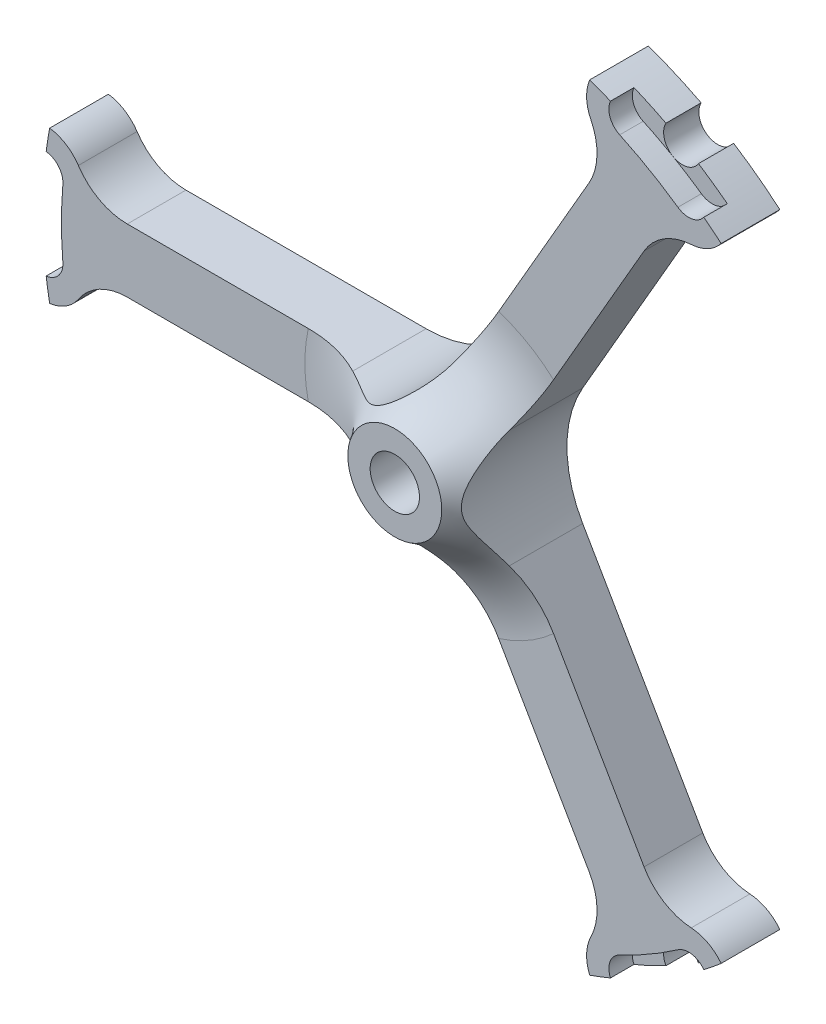
SolidWorks part; units mm, degrees
ref_plane "Plan de face" through (0, 0, 0) normal (0, 0, 1) x (1, 0, 0)
ref_plane "Plan de dessus" through (0, 0, 0) normal (0, 1, 0) x (1, 0, 0)
ref_plane "Plan de droite" through (0, 0, 0) normal (1, 0, 0) x (0, 0, -1)
sketch "Esquisse1" plane through (0, 0, 0) normal (0, 0, 1) x (1, 0, 0)
  line L19 (-1000, 0) -> (49000, 0) construction
  line L21 (-27.7888, 2.7) -> (-7.3323, 2.7)
  line L23 (-27.7888, -2.7) -> (-7.3323, -2.7)
  line L33 (16.2327, 22.7158) -> (6.0044, 5)
  line L34 (11.5561, 25.4158) -> (1.3279, 7.7)
  line L35 (11.5561, -25.4158) -> (1.3279, -7.7)
  line L36 (16.2327, -22.7158) -> (6.0044, -5)
  arc A0 (-34.3972, 6.4678) -> (-34.6976, 4.5906) centre (0, 0) ccw
  arc A7 (-33.2771, 2.8629) -> (-34.6976, 4.5906) centre (-34.8712, 3) ccw
  arc A8 (-33.2771, -2.8629) -> (-34.6976, -4.5906) centre (-34.8712, -3) cw
  arc A12 (-33.2771, 2.8629) -> (-33.2771, -2.8629) centre (0, 0) ccw
  arc A13 (-31.9549, 4.9353) -> (-34.3972, 6.4678) centre (-34.8712, 3) ccw
  arc A14 (-31.9549, -4.9353) -> (-34.3972, -6.4678) centre (-34.8712, -3) cw
  arc A15 (-34.6976, -4.5906) -> (-34.3972, -6.4678) centre (0, 0) ccw
  arc A16 (-27.7888, -2.7) -> (-31.9549, -4.9353) centre (-27.7888, -7.7) ccw
  arc A17 (-27.7888, 2.7) -> (-31.9549, 4.9353) centre (-27.7888, 7.7) cw
  arc A48 (22.7998, 26.555) -> (21.3244, 27.7538) centre (0, 0) ccw
  arc A49 (19.1178, 27.3874) -> (21.3244, 27.7538) centre (20.0337, 28.6993) ccw
  arc A50 (14.1592, 30.2502) -> (13.3733, 32.3443) centre (14.8375, 31.6993) cw
  arc A51 (19.1178, 27.3874) -> (14.1592, 30.2502) centre (0, 0) ccw
  arc A52 (20.2516, 25.2061) -> (22.7998, 26.555) centre (20.0337, 28.6993) ccw
  arc A53 (11.7034, 30.1414) -> (11.5974, 33.0227) centre (14.8375, 31.6993) cw
  arc A54 (13.3733, 32.3443) -> (11.5974, 33.0227) centre (0, 0) ccw
  arc A55 (11.5561, 25.4158) -> (11.7034, 30.1414) centre (7.226, 27.9158) ccw
  arc A56 (16.2327, 22.7158) -> (20.2516, 25.2061) centre (20.5628, 20.2158) cw
  arc A57 (11.5974, -33.0227) -> (13.3733, -32.3443) centre (0, 0) ccw
  arc A58 (14.1592, -30.2502) -> (13.3733, -32.3443) centre (14.8375, -31.6993) ccw
  arc A59 (19.1178, -27.3874) -> (21.3244, -27.7538) centre (20.0337, -28.6993) cw
  arc A60 (14.1592, -30.2502) -> (19.1178, -27.3874) centre (0, 0) ccw
  arc A61 (11.7034, -30.1414) -> (11.5974, -33.0227) centre (14.8375, -31.6993) ccw
  arc A62 (20.2516, -25.2061) -> (22.7998, -26.555) centre (20.0337, -28.6993) cw
  arc A63 (21.3244, -27.7538) -> (22.7998, -26.555) centre (0, 0) ccw
  arc A64 (16.2327, -22.7158) -> (20.2516, -25.2061) centre (20.5628, -20.2158) ccw
  arc A65 (11.5561, -25.4158) -> (11.7034, -30.1414) centre (7.226, -27.9158) cw
  arc A66 (-7.3323, -2.7) -> (1.3279, -7.7) centre (-7.3323, -12.7) cw
  arc A67 (6.0044, -5) -> (6.0044, 5) centre (14.6647, 0) cw
  arc A68 (1.3279, 7.7) -> (-7.3323, 2.7) centre (-7.3323, 12.7) cw
  point P38 (0, 0)
  point P50 (3.1177, 0)
  point P55 (0, 0)
  point P56 (0, 0)
  point P80 (0, 0)
  dimension "D1" = 70
  dimension "D3" = 3
  dimension "D2" = 3.2
  dimension "D4" = 5
  dimension "D5" = 10
extrude "Boss.-Extru.1" add sketch "Esquisse1" along normal blind 5
sketch "Esquisse7" plane through (0, 0, 0) normal (0, 0, -1) x (-1, 0, 0)
  line L0 (-1000, 0) -> (49000, 0) construction
  arc A0 (34.6976, -4.5906) -> (34.6976, 4.5906) centre (0, 0) ccw
  arc A2 (33.2771, -2.8629) -> (33.2771, 2.8629) centre (0, 0) ccw
  arc A4 (34.9634, 1.5996) -> (34.9634, -1.5996) centre (35, 0) ccw
  arc A5 (34.6976, 4.5906) -> (33.2771, 2.8629) centre (34.8712, 3) ccw
  arc A6 (33.2771, -2.8629) -> (33.2771, 2.8629) centre (0, 0) ccw construction
  arc A7 (34.6976, -4.5906) -> (33.2771, -2.8629) centre (34.8712, -3) cw
  arc A8 (-21.3244, -27.7538) -> (-13.3733, -32.3443) centre (0, 0) ccw
  arc A9 (-19.1178, -27.3874) -> (-14.1592, -30.2502) centre (0, 0) ccw
  arc A10 (-16.0964, -31.079) -> (-18.867, -29.4794) centre (-17.5, -30.3109) ccw
  arc A11 (-13.3733, -32.3443) -> (-14.1592, -30.2502) centre (-14.8375, -31.6993) ccw
  arc A12 (-21.3244, -27.7538) -> (-19.1178, -27.3874) centre (-20.0337, -28.6993) cw
  arc A13 (-13.3733, 32.3443) -> (-21.3244, 27.7538) centre (0, 0) ccw
  arc A14 (-14.1592, 30.2502) -> (-19.1178, 27.3874) centre (0, 0) ccw
  arc A15 (-18.867, 29.4794) -> (-16.0964, 31.079) centre (-17.5, 30.3109) ccw
  arc A16 (-21.3244, 27.7538) -> (-19.1178, 27.3874) centre (-20.0337, 28.6993) ccw
  arc A17 (-13.3733, 32.3443) -> (-14.1592, 30.2502) centre (-14.8375, 31.6993) cw
  point P36 (0, 0)
  arc M44 (34.6976, -4.5906) -> (33.2771, -2.8629) centre (34.8712, -3) cw
  arc M45 (33.2771, -2.8629) -> (33.2771, 2.8629) centre (0, 0) ccw
  arc M46 (33.2771, 2.8629) -> (34.6976, 4.5906) centre (34.8712, 3) cw
  arc M56 (-13.3733, 32.3443) -> (-14.1592, 30.2502) centre (-14.8375, 31.6993) cw
  arc M57 (-14.1592, 30.2502) -> (-19.1178, 27.3874) centre (0, 0) ccw
  arc M58 (-19.1178, 27.3874) -> (-21.3244, 27.7538) centre (-20.0337, 28.6993) cw
  arc M68 (-21.3244, -27.7538) -> (-19.1178, -27.3874) centre (-20.0337, -28.6993) cw
  arc M69 (-19.1178, -27.3874) -> (-14.1592, -30.2502) centre (0, 0) ccw
  arc M70 (-14.1592, -30.2502) -> (-13.3733, -32.3443) centre (-14.8375, -31.6993) cw
  dimension "D1" = 3.2
  dimension "D3" = 3.2
  dimension "D4" = 70
  dimension "D2" = 3
extrude "Boss.-Extru.5" add sketch "Esquisse7" against normal blind 3 contours A4 A0 A2 M46 | A4 A0 M45 M44 | A10 A8 A9 M70 | A10 A8 M69 M68 | A15 A13 M57 M56 | A15 A13 A14 M58 region at (-34.0862, -2.7129, 0) region at (-34.0862, 2.7129, 0) region at (19.3926, -28.1631, 0) region at (14.6937, -30.876, 0) region at (14.6937, 30.876, 0) region at (19.3926, 28.1631, 0)
sketch "Esquisse4" plane through (0, 0, 5) normal (0, 0, 1) x (1, 0, 0)
  circle A1 centre (0, 0) radius 4
  dimension "D1" = 8
extrude "Boss.-Extru.3" add sketch "Esquisse4" along normal blind 5
sketch "Esquisse5" plane through (0, 0, 10) normal (0, 0, 1) x (1, 0, 0)
  circle A0 centre (0, 0) radius 2.1
  dimension "D1" = 4.2
extrude "Enlèv. mat.-Extru.2" cut sketch "Esquisse5" against normal blind 3
fillet "Congé1" radius 10 1 edges at (4, 0, 5)
sketch "Esquisse6" plane through (0, 0, 7) normal (0, 0, 1) x (1, 0, 0)
  circle A0 centre (0, 0) radius 1.5
  dimension "D1" = 3
extrude "Enlèv. mat.-Extru.3" cut sketch "Esquisse6" against normal up to next
